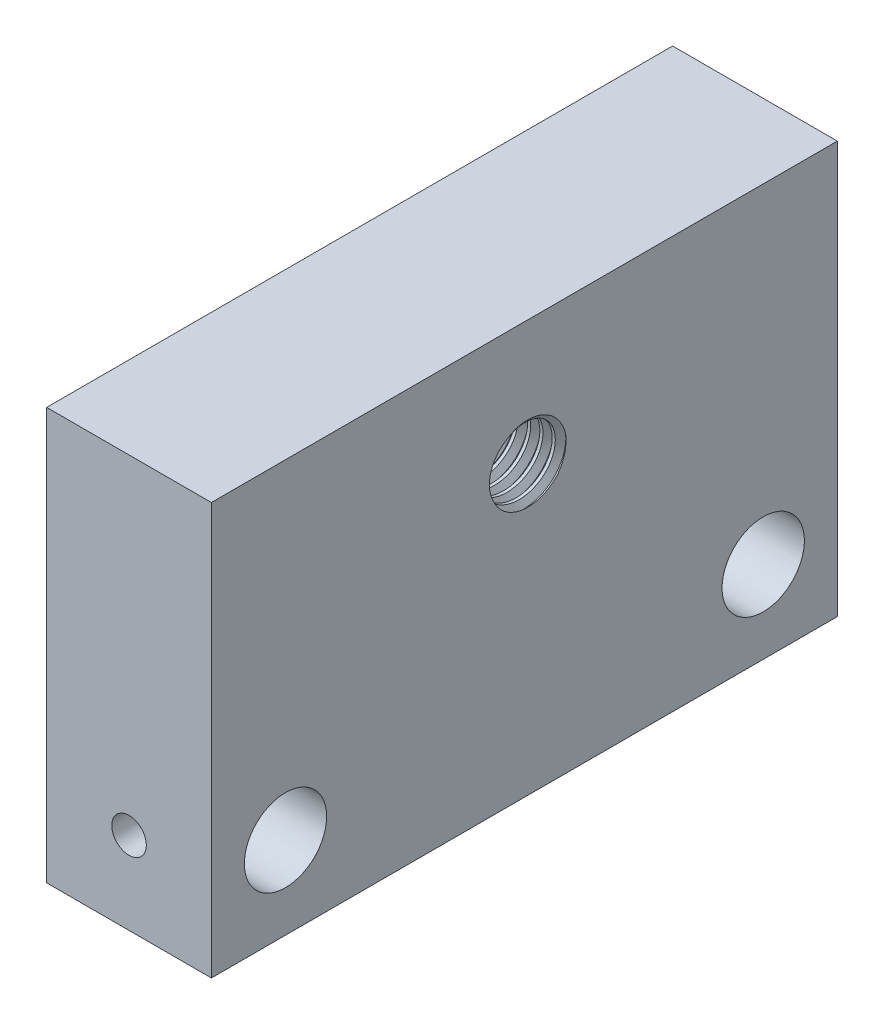
SolidWorks part; units mm, degrees
ref_plane "Front Plane" through (0, 0, 0) normal (0, 0, 1) x (1, 0, 0)
ref_plane "Top Plane" through (0, 0, 0) normal (0, 1, 0) x (1, 0, 0)
ref_plane "Right Plane" through (0, 0, 0) normal (1, 0, 0) x (0, 0, -1)
sketch "Sketch1" plane through (0, 0, 0) normal (0, 1, 0) x (1, 0, 0)
  line L1 (10, 38) -> (-10, 38)
  line L2 (10, 38) -> (10, -38)
  line L3 (10, -38) -> (-10, -38)
  line L4 (-10, 38) -> (-10, -38)
  line L5 (10, 38) -> (-10, -38) construction
  line L6 (10, -38) -> (-10, 38) construction
  point P0 (0, 0)
  dimension "D1" = 20
  dimension "D2" = 76
extrude "Boss-Extrude1" add sketch "Sketch1" along normal blind 50
sketch "Sketch2" plane through (10, 0, 0) normal (1, 0, 0) x (0, 0, -1)
  line L0 (0, 41.9858) -> (0, -3.6541) construction
  line L1 (-38, 0) -> (38, 0) construction
  circle A0 centre (-29, 10) radius 5
  circle A1 centre (29, 10) radius 5
  dimension "D1" = 10
  dimension "D2" = 10
  dimension "D3" = 58
hole_wizard "M10 Tapped Hole1" positions "Sketch5" profile "Sketch6" tap size "M10" standard "ISO" end condition through all
sketch "Sketch5" plane through (10, 0, 0) normal (1, 0, 0) x (0, 0, -1)
  line L0 (0, 41.9858) -> (0, -3.6541) construction
  point P0 (0, 35)
  point P4 (0, 34.6118)
  dimension "D1" = 35
sketch "Sketch6" plane through (10, 35, 0) normal (0, 1, 0) x (0, 0, -1)
  line L0 (0, 0) -> (0, 20)
  line L1 (0, 20) -> (4.25, 20)
  line L2 (4.25, 20) -> (4.25, 0)
  line L5 (4.25, 0) -> (0, 0)
  line L11 (0, -6.35) -> (0, 107.95) construction
  dimension "Thru Tap Drill Dia." = 8.5
  dimension "Thru Tap Drill Depth" = 20
cosmetic thread "Hole Thread1"
thread "Thread1" pitch 1.5 method cut profile "Thread Profile1" start angle 0, offset 0, length 20, pitch 1.5, diameter 8.5
ref_plane "Plane1" through (-10, 35, -4.25) normal (0, -1, 0) x (0, 0, -1)
sketch "Thread Profile1" plane through (-10, 35, -4.25) normal (0, -1, 0) x (0, 0, -1)
  line L0 (0, 0) -> (0, 1.5) construction
  line L1 (0, 0) -> (0.8119, 0.4687)
  line L2 (0.8119, 0.4687) -> (0.8119, 0.6562)
  line L3 (0.8119, 0.6562) -> (0, 1.125)
  line L4 (0.8119, 0.5625) -> (0, 0.5625) construction
  line L11 (0, 0) -> (0, 1.125)
  point P2 (0, 0)
  dimension "Pitch" = 1.5
  dimension "Profile_Angle" = 60
  dimension "Profile_Land" = 0.1875
  dimension "Profile_Height" = 0.8119
extrude "Cut-Extrude2" cut sketch "Sketch2" against normal through all
hole_wizard "M5 Tapped Hole2" positions "Sketch12" profile "Sketch13" tap size "M5" standard "ISO"
sketch "Sketch12" plane through (0, 0, -38) normal (0, 0, -1) x (-1, 0, 0)
  point P0 (0, 10)
  point P5 (0, 10)
  point P7 (0, 10)
  point P9 (0, 10)
  dimension "D1" = 10
sketch "Sketch13" plane through (0, 10, -38) normal (1, 0, 0) x (0, 1, 0)
  line L0 (0, 0) -> (0, 11.2618)
  line L1 (0, 11.2618) -> (2.1, 10)
  line L2 (2.1, 10) -> (2.1, 0)
  line L5 (2.1, 0) -> (0, 0)
  line L10 (0, 11.2618) -> (-2.1, 10) construction
  line L11 (0, -6.35) -> (0, 107.95) construction
  dimension "Tap Drill Dia." = 4.2
  dimension "Tap Drill Depth" = 10
  dimension "Drill Angle" = 118
cosmetic thread "Hole Thread7"
hole_wizard "M5 Tapped Hole4" positions "Sketch16" profile "Sketch17" tap size "M5" standard "ISO"
sketch "Sketch16" plane through (0, 0, 38) normal (0, 0, 1) x (1, 0, 0)
  line L0 (-10, 0) -> (10, 0) construction
  point P0 (0, 10)
  dimension "D1" = 10
sketch "Sketch17" plane through (0, 10, 38) normal (1, 0, 0) x (0, -1, 0)
  line L0 (0, 0) -> (0, 11.2618)
  line L1 (0, 11.2618) -> (2.1, 10)
  line L2 (2.1, 10) -> (2.1, 0)
  line L5 (2.1, 0) -> (0, 0)
  line L10 (0, 11.2618) -> (-2.1, 10) construction
  line L11 (0, -6.35) -> (0, 107.95) construction
  dimension "Tap Drill Dia." = 4.2
  dimension "Tap Drill Depth" = 10
  dimension "Drill Angle" = 118
cosmetic thread "Hole Thread5"
